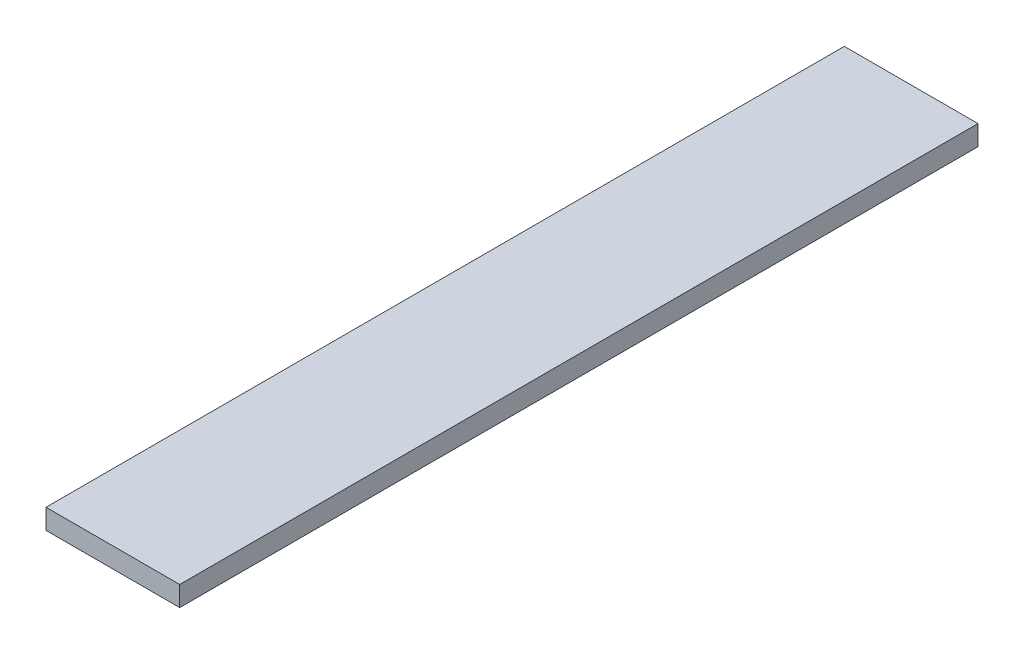
SolidWorks part; units mm, degrees
material "Pine"
ref_plane "Front Plane" through (0, 0, 0) normal (0, 0, 1) x (1, 0, 0)
ref_plane "Top Plane" through (0, 0, 0) normal (0, 1, 0) x (1, 0, 0)
ref_plane "Right Plane" through (0, 0, 0) normal (1, 0, 0) x (0, 0, -1)
sketch "Sketch1" plane through (0, 0, 0) normal (0, 1, 0) x (1, 0, 0)
  line L1 (0, 0) -> (127, 0)
  line L2 (0, 0) -> (0, -758.19)
  line L3 (0, -758.19) -> (127, -758.19)
  line L4 (127, 0) -> (127, -758.19)
  dimension "D1" = 127
  dimension "D2" = 758.19
extrude "Boss-Extrude1" add sketch "Sketch1" along normal blind 19.05
